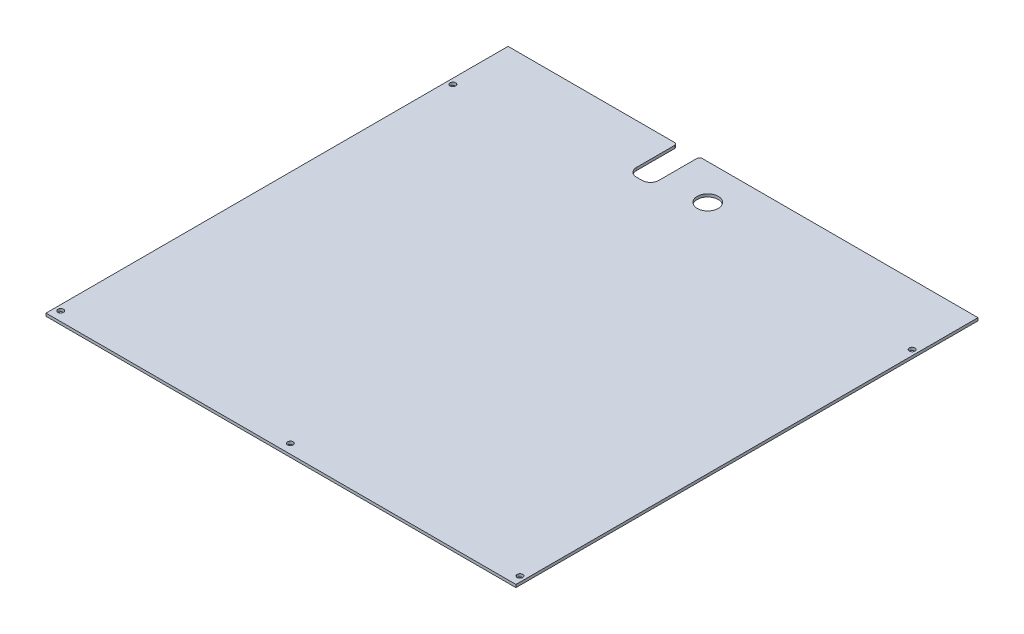
SolidWorks part; units mm, degrees
note: The reader was unsure of these and kept them because the rebuilt part matched: thickness of "Brida base2", "Chapa metálica(12)", "Chapa metálica(21)", "Chapa metálica(22)", "Chapa metálica(23)".
material "Poliestireno"
ref_plane "Alzado" through (0, 0, 0) normal (0, 0, 1) x (1, 0, 0)
ref_plane "Planta" through (0, 0, 0) normal (0, 1, 0) x (1, 0, 0)
ref_plane "Vista lateral" through (0, 0, 0) normal (1, 0, 0) x (0, 0, -1)
sketch "Croquis12" plane through (0, 0, 0) normal (0, 1, 0) x (1, 0, 0)
  line L0 (0, 0) -> (0, 121.41) construction
  line L1 (-167.5, -207.99) -> (167.5, -207.99)
  line L2 (-167.5, -207.99) -> (-167.5, 121.41)
  line L3 (-167.5, 121.41) -> (167.5, 121.41)
  line L4 (167.5, -207.99) -> (167.5, 121.41)
  point P14 (167.5, 121.41)
  point P17 (-167.5, 121.41)
  dimension "D1" = 335
  dimension "D2" = 207.99
  dimension "D3" = 121.41
base flange "Brida base2" sketch "Croquis12" thickness 2 reverse thickness direction no parameters "D1"=1
sketch "Croquis25" plane through (0, 0, 0) normal (0, 1, 0) x (1, 0, 0)
  line L0 (0, 0) -> (0, -48.7685) construction
  line L2 (-159.058, -201.3) -> (150.1867, -201.3) construction
  dimension "D2" = 201.3
sketch "Croquis27" plane through (0, 0, 0) normal (0, 1, 0) x (1, 0, 0)
  line L0 (0, 0) -> (0, -88.775) construction
  line L1 (-159.058, -201.3) -> (150.1867, -201.3) construction
  line L2 (-163.7, -201.3) -> (163.7, -201.3) construction
  circle A0 centre (-163.7, -201.3) radius 2
  circle A1 centre (-163.7, 78.26) radius 2
  circle A2 centre (163.7, 78.26) radius 2
  circle A3 centre (163.7, -201.3) radius 2
  circle A4 centre (0, -201.3) radius 2
  dimension "D1" = 4
  dimension "D4" = 327.4
  dimension "D2" = 78.26
extrude "Cortar-Extruir6" cut sketch "Croquis27" against normal up to next normal cut yes
sketch "Croquis28" plane through (0, 0, 0) normal (0, 1, 0) x (1, 0, 0)
  line L1 (-167.5, -207.99) -> (167.5, -207.99) construction
  circle A0 centre (0, 96.25) radius 7.5
  dimension "D1" = 304.24
  dimension "D2" = 15
extrude "Cortar-Extruir7" cut sketch "Croquis28" against normal up to next normal cut yes
sketch "Croquis29" plane through (0, 0, 0) normal (0, 1, 0) x (1, 0, 0)
  line L0 (-39, 86.41) -> (-39, 125.7663) construction
  line L1 (-47, 121.41) -> (-31, 121.41)
  line L2 (-47, 121.41) -> (-47, 86.41)
  line L3 (-47, 86.41) -> (-31, 86.41)
  line L4 (-31, 121.41) -> (-31, 86.41)
  line L5 (167.5, 121.41) -> (-167.5, 121.41) construction
  circle A2 centre (0, 96.25) radius 7.5 construction
  dimension "D1" = 39
  dimension "D2" = 16
  dimension "D3" = 35
extrude "Cortar-Extruir8" cut sketch "Croquis29" against normal through all normal cut yes
fillet "Redondeo1" radius 6 2 edges at (-31, -1, -86.41) (-47, -1, -86.41)
fillet "Redondeo2" radius 2 2 edges at (-31, -1, -121.41) (-47, -1, -121.41)
sketch "Líneas de pliegue3" [suppressed] plane through (0, 0, 0) normal (0, 1, 0) x (1, 0, 0)
sketch "Cuadro delimitador3" [suppressed] plane through (0, 0, 0) normal (0, 1, 0) x (1, 0, 0)
sheet metal parameters "Chapa metálica(12)" thickness 2 parameters "D1"=1
flat pattern "Chapa desplegada(12)" [suppressed]
sketch "Líneas de pliegue4" plane through (0, 0, 0) normal (0, 1, 0) x (1, 0, 0)
sketch "Cuadro delimitador4" [suppressed] plane through (0, 0, 0) normal (0, 1, 0) x (1, 0, 0)
sheet metal parameters "Chapa metálica(21)" thickness 2 parameters "D1"=1, "D7"=3
flat pattern "Chapa desplegada(12)"
sketch "Líneas de pliegue4" plane through (0, 0, 0) normal (0, 1, 0) x (1, 0, 0)
sketch "Cuadro delimitador4" [suppressed] plane through (0, 0, 0) normal (0, 1, 0) x (1, 0, 0)
sheet metal parameters "Chapa metálica(22)" thickness 2 parameters "D1"=1, "D7"=3
flat pattern "Chapa desplegada(12)"
sketch "Líneas de pliegue4" plane through (0, 0, 0) normal (0, 1, 0) x (1, 0, 0)
sketch "Cuadro delimitador4" [suppressed] plane through (0, 0, 0) normal (0, 1, 0) x (1, 0, 0)
sheet metal parameters "Chapa metálica(23)" thickness 2 parameters "D1"=1, "D7"=3
flat pattern "Chapa desplegada(12)"
sketch "Líneas de pliegue4" plane through (0, 0, 0) normal (0, 1, 0) x (1, 0, 0)
sketch3d "Cuadro delimitador4" [suppressed]
  line L0 (167.5, 121.41, 0) -> (-167.5, 121.41, 0) construction
  line L1 (167.5, -207.99, 0) -> (-167.5, -207.99, 0) construction
  line L2 (167.5, 121.41, 0) -> (167.5, -207.99, 0) construction
  line L3 (-167.5, 121.41, 0) -> (-167.5, -207.99, 0) construction
